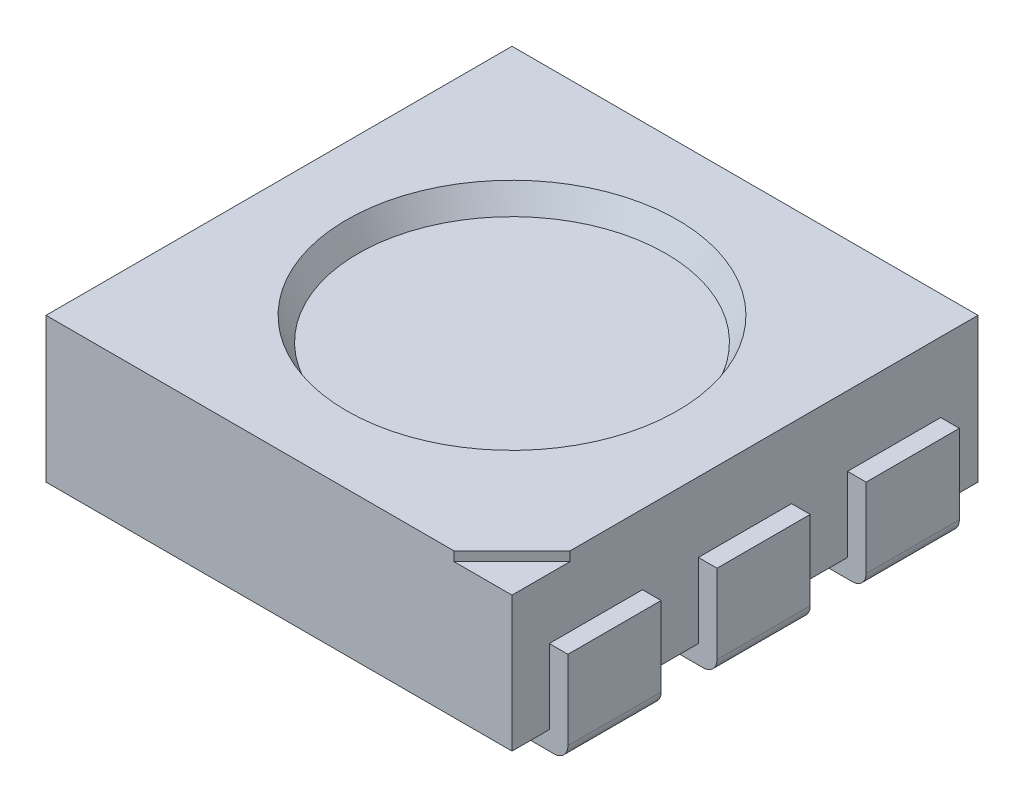
SolidWorks part; units mm, degrees
note: '?' marks a value the reader was unsure of.
ref_plane "Front Plane" through (0, 0, 0) normal (0, 0, 1) x (1, 0, 0)
ref_plane "Top Plane" through (0, 0, 0) normal (0, 1, 0) x (1, 0, 0)
ref_plane "Right Plane" through (0, 0, 0) normal (1, 0, 0) x (0, 0, -1)
sketch "Sketch1" plane through (0, 0, 0) normal (0, 1, 0) x (1, 0, 0)
  line L1 (-2.5, -2.5) -> (2.5, -2.5)
  line L2 (-2.5, -2.5) -> (-2.5, 2.5)
  line L3 (-2.5, 2.5) -> (2.5, 2.5)
  line L4 (2.5, -2.5) -> (2.5, 2.5)
  line L5 (-2.5, -2.5) -> (2.5, 2.5) construction
  line L6 (-2.5, 2.5) -> (2.5, -2.5) construction
  point P0 (0, 0)
  dimension "D1" = 5
  dimension "D2" = 5
extrude "Boss-Extrude1" add sketch "Sketch1" along normal blind 1.55
sketch "Sketch2" plane through (0, 1.55, 0) normal (0, 1, 0) x (1, 0, 0)
  circle A0 centre (0, 0) radius 1.775
  dimension "D1" = 3.55
hole_wizard "CSK SLOT for M2 Flat Head Machine Screw1" positions "Sketch4" profile "Sketch5" size "M2" standard "ANSI Metric" slot yes
sketch "Sketch4" plane through (0, 1.55, 0) normal (0, 1, 0) x (1, 0, 0)
  point P0 (0, 0)
sketch "Sketch5" plane through (0, 1.55, 0) normal (1, 0, 0) x (0, 0, 1)
  line L0 (0, 0) -> (0, 0.25)
  line L1 (0, 0.25) -> (1.65, 0.25)
  line L2 (1.65, 0.25) -> (1.65, 0.2507)
  line L3 (1.65, 0.2507) -> (1.775, 0)
  line L5 (1.775, 0) -> (0, 0)
  line L6 (-1.65, 0.2507) -> (-1.775, 0) construction
  line L10 (0, 0.25) -> (-1.65, 0.25) construction
  line L11 (0, -6.35) -> (0, 107.95) construction
  dimension "Hole Dia." = 3.3
  dimension "Hole Depth" = 0.25
  dimension "Near C'Sink Dia." = 3.55
  dimension "Near C'Sink Angle" = 53
  dimension "Drill Angle" = 180
sketch "Sketch6" plane through (-2.5, 0, 0) normal (-1, 0, 0) x (0, 0, 1)
  line L0 (-2.5, 0) -> (2.5, 0) construction
  line L1 (-2.1, 0) -> (-1.1, 0)
  line L2 (-2.1, 0) -> (-2.1, 0.8)
  line L3 (-2.1, 0.8) -> (-1.1, 0.8)
  line L4 (-1.1, 0) -> (-1.1, 0.8)
  line L5 (-2.5, 1.55) -> (-2.5, 0) construction
  line L7 (-0.5, 0) -> (0.5, 0)
  line L8 (-0.5, 0) -> (-0.5, 0.8)
  line L9 (-0.5, 0.8) -> (0.5, 0.8)
  line L10 (0.5, 0) -> (0.5, 0.8)
  line L11 (1.1, 0) -> (2.1, 0)
  line L12 (1.1, 0) -> (1.1, 0.8)
  line L13 (1.1, 0.8) -> (2.1, 0.8)
  line L14 (2.1, 0) -> (2.1, 0.8)
  line M1 (-2.5, 0) -> (2.5, 0)
  dimension "D1" = 0.4
  dimension "D2" = 0.6
  dimension "D3" = 0.6
  dimension "D4" = 0.8
  dimension "D5" = 1
extrude "Boss-Extrude3" add sketch "Sketch6" along normal blind 0.2 contours L10 L9 L8 M1 | L14 L13 L12 M1 | L2 L3 L4 L1
sketch "Sketch7" plane through (0, 0, 0) normal (0, -1, 0) x (1, 0, 0)
  line L1 (-2.7, -2.1) -> (-1.7, -2.1)
  line L2 (-2.7, -2.1) -> (-2.7, -1.1)
  line L3 (-2.7, -1.1) -> (-1.7, -1.1)
  line L4 (-1.7, -2.1) -> (-1.7, -1.1)
  line L5 (-2.7, -0.5) -> (-1.7, -0.5)
  line L6 (-2.7, -0.5) -> (-2.7, 0.5)
  line L7 (-2.7, 0.5) -> (-1.7, 0.5)
  line L8 (-1.7, -0.5) -> (-1.7, 0.5)
  line L9 (-2.7, 1.1) -> (-1.7, 1.1)
  line L10 (-2.7, 1.1) -> (-2.7, 2.1)
  line L11 (-2.7, 2.1) -> (-1.7, 2.1)
  line L12 (-1.7, 1.1) -> (-1.7, 2.1)
  dimension "D1" = 1
  dimension "D2" = 0.6
  dimension "D3" = 0.6
extrude "Boss-Extrude5" add sketch "Sketch7" along normal blind 0.2
fillet "Fillet1" radius 0.15 3 edges at (-2.7, -0.2, 1.6) (-2.7, -0.2, 0) (-2.7, -0.2, -1.6)
ref_axis "Axis1" through (0, 0, 2.5) along (0, 0, -1)?
ref_plane "Plane1" through (0, 0, 0) normal (-1, 0, 0) x (0, 0, 1)
mirror "Mirror1" about plane through (0, 0, 0) normal (-1, 0, 0) of "Fillet1", "Boss-Extrude3", "Boss-Extrude5"
sketch "Sketch9" plane through (0, 1.55, 0) normal (0, 1, 0) x (1, 0, 0)
  line L0 (1.8782, -2.5) -> (2.5, -1.8782)
  line L1 (-2.5, -2.5) -> (2.5, -2.5) construction
  line L2 (2.5, -2.5) -> (2.5, 2.5) construction
  line L3 (1.8782, -2.5) -> (2.5, -2.5)
  line L4 (2.5, -2.5) -> (2.5, -1.8782)
extrude "Cut-Extrude2" cut sketch "Sketch9" against normal blind 0.1
